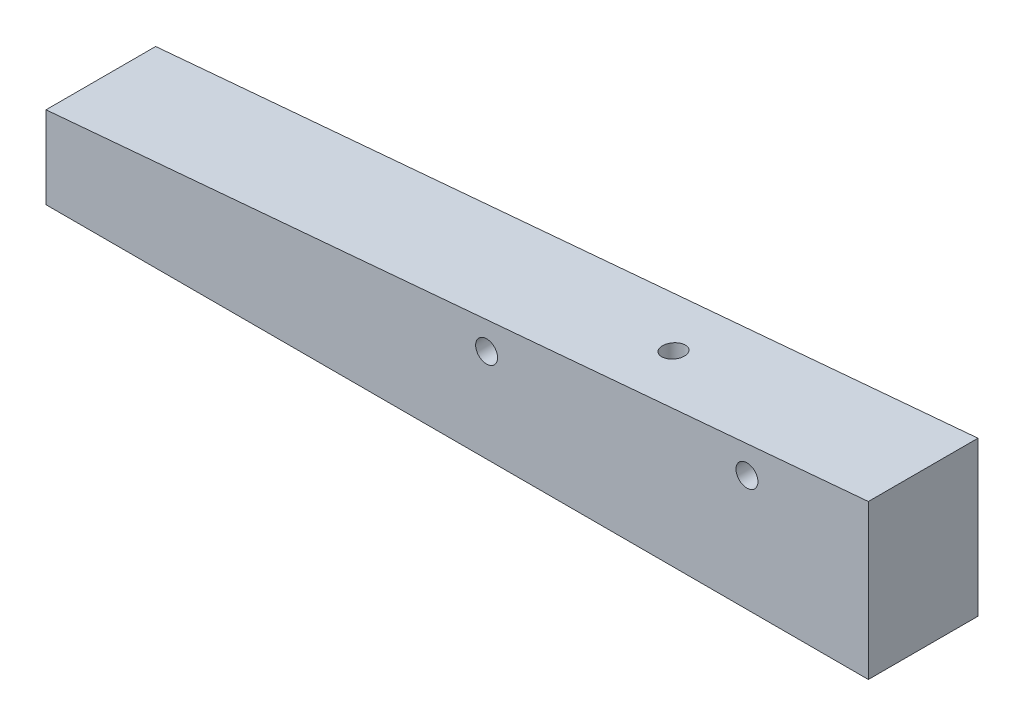
SolidWorks part; units mm, degrees
ref_plane "Front Plane" through (0, 0, 0) normal (0, 0, 1) x (1, 0, 0)
ref_plane "Top Plane" through (0, 0, 0) normal (0, 1, 0) x (1, 0, 0)
ref_plane "Right Plane" through (0, 0, 0) normal (1, 0, 0) x (0, 0, -1)
sketch "Sketch1" plane through (0, 0, 0) normal (0, 0, 1) x (1, 0, 0)
  line L3 (45.5436, 28.1233) -> (-104.4564, 15)
  line L4 (-104.4564, 15) -> (-104.4564, 0)
  line L5 (-104.4564, 0) -> (45.5436, 0)
  line L7 (45.5436, 28.1233) -> (45.5436, 0)
  line L8 (55, 0) -> (-55, 0) construction
  dimension "D1" = 150
  dimension "D2" = 5
  dimension "D3" = 15
extrude "Boss-Extrude1" add sketch "Sketch1" along normal mid plane 20
sketch "Sketch2" plane through (0, 0, 0) normal (0, -1, 0) x (1, 0, 0)
  circle A0 centre (0, 0) radius 2
  dimension "D1" = 4
extrude "Cut-Extrude1" cut sketch "Sketch2" along direction (0, 1, 0) on the side against the normal through all both and the other way through all
sketch "Sketch3" plane through (0, 0, -10) normal (0, 0, -1) x (-1, 0, 0)
  line L0 (-22.9644, 26.1479) -> (-23.4002, 21.1669) construction
  line L2 (-45.5436, 28.1233) -> (104.4564, 15) construction
  line L4 (24.5252, 21.9931) -> (24.0894, 17.0121) construction
  circle A0 centre (-23.4002, 21.1669) radius 2
  circle A1 centre (24.0894, 17.0121) radius 2
  dimension "D3" = 90
  dimension "D5" = 4
  dimension "D6" = 4
  dimension "D1" = 90
  dimension "D2" = 5
  dimension "D4" = 5
extrude "Cut-Extrude2" cut sketch "Sketch3" against normal through all both and the other way through all
